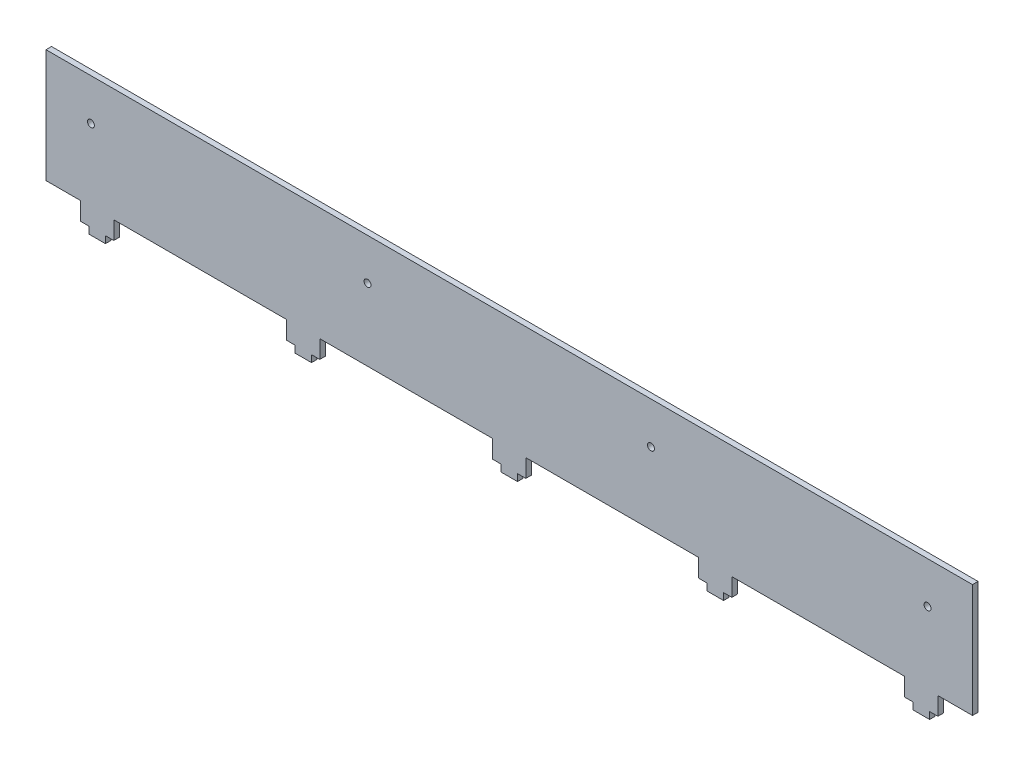
SolidWorks part; units mm, degrees
ref_plane "Спереди" through (0, 0, 0) normal (0, 0, 1) x (1, 0, 0)
ref_plane "Сверху" through (0, 0, 0) normal (0, 1, 0) x (1, 0, 0)
ref_plane "Справа" through (0, 0, 0) normal (1, 0, 0) x (0, 0, -1)
sketch "Эскиз1" plane through (0, 0, 0) normal (0, 0, 1) x (1, 0, 0)
  line L1 (-335, -47.5) -> (335, -47.5)
  line L2 (-335, -47.5) -> (-335, 47.5)
  line L3 (-335, 47.5) -> (335, 47.5)
  line L4 (335, -47.5) -> (335, 47.5)
  line L5 (0, 47.5) -> (0, -47.5) construction
  line L6 (-335, 0) -> (335, 0) construction
  point P0 (0, 0)
  dimension "D1" = 95
  dimension "D2" = 670
extrude "Бобышка-Вытянуть1" add sketch "Эскиз1" along normal mid plane 4
sketch "Эскиз2" plane through (0, 0, 2) normal (0, 0, 1) x (1, 0, 0)
  line L0 (-335, -47.5) -> (335, -47.5) construction
  line L9 (-435, -34.5) -> (-310, -34.5)
  line L10 (-435, -34.5) -> (-435, -47.5)
  line L11 (-435, -47.5) -> (-310, -47.5)
  line L12 (-310, -34.5) -> (-310, -47.5)
  line L13 (335, 47.5) -> (-335, 47.5) construction
  line L14 (-286, -34.5) -> (-161, -34.5)
  line L15 (-286, -34.5) -> (-286, -47.5)
  line L16 (-286, -47.5) -> (-161, -47.5)
  line L17 (-161, -34.5) -> (-161, -47.5)
  line L18 (-137, -34.5) -> (-12, -34.5)
  line L19 (-137, -34.5) -> (-137, -47.5)
  line L20 (-137, -47.5) -> (-12, -47.5)
  line L21 (-12, -34.5) -> (-12, -47.5)
  line L22 (12, -34.5) -> (137, -34.5)
  line L23 (12, -34.5) -> (12, -47.5)
  line L24 (12, -47.5) -> (137, -47.5)
  line L25 (137, -34.5) -> (137, -47.5)
  line L26 (161, -34.5) -> (286, -34.5)
  line L27 (161, -34.5) -> (161, -47.5)
  line L28 (161, -47.5) -> (286, -47.5)
  line L29 (286, -34.5) -> (286, -47.5)
  line L30 (310, -34.5) -> (435, -34.5)
  line L31 (310, -34.5) -> (310, -47.5)
  line L32 (310, -47.5) -> (435, -47.5)
  line L33 (435, -34.5) -> (435, -47.5)
  point P25 (-137, -41)
  point P26 (137, -41)
  dimension "D6" = 125
  dimension "D3" = 125
  dimension "D4" = 125
  dimension "D9" = 125
  dimension "D11" = 125
  dimension "D5" = 24
  dimension "D2" = 24
  dimension "D7" = 24
  dimension "D8" = 24
  dimension "D10" = 24
  dimension "D12" = 125
  dimension "D13" = 12
  dimension "D14" = 82
extrude "Вырез-Вытянуть1" cut sketch "Эскиз2" against normal through all
sketch "Эскиз3" [suppressed] plane through (0, 0, 2) normal (0, 0, 1) x (1, 0, 0)
  line L0 (-328, 5.9544) -> (-328, -6.0456)
  line L1 (-328, -6.0456) -> (-318, -6.0456)
  line L2 (-318, -6.0456) -> (-318, -20.0456)
  line L3 (-318, -20.0456) -> (318, -20.0456)
  line L4 (318, -20.0456) -> (318, -6.0456)
  line L5 (318, -6.0456) -> (328, -6.0456)
  line L6 (328, -6.0456) -> (328, 5.9544)
  line L7 (328, 5.9544) -> (290, 5.9544)
  line L8 (290, 5.9544) -> (280, 35.5)
  line L9 (280, 35.5) -> (240, 35.5)
  line L10 (240, 35.5) -> (230, 5.9544)
  line L11 (230, 5.9544) -> (-230, 5.9544)
  line L12 (-230, 5.9544) -> (-240, 35.5)
  line L13 (-240, 35.5) -> (-280, 35.5)
  line L14 (-280, 35.5) -> (-290, 5.9544)
  line L15 (-290, 5.9544) -> (-328, 5.9544)
  line L16 (0, 0) -> (0, 91.1092) construction
  line L17 (-260, 35.5) -> (-260, 12.7826) construction
  line L18 (260, 35.5) -> (260, 0) construction
  line L19 (-12, -35.0456) -> (-137, -35.0456) construction
  line L20 (-335, 47.5) -> (-335, -35.0456) construction
  line L21 (335, 47.5) -> (-335, 47.5) construction
  dimension "D1" = 15
  dimension "D2" = 14
  dimension "D3" = 12
  dimension "D4" = 60
  dimension "D5" = 38
  dimension "D6" = 7
  dimension "D7" = 17
  dimension "D8" = 12
  dimension "D9" = 40
extrude "Вырез-Вытянуть2" [suppressed] cut sketch "Эскиз3" against normal through all
fillet "Скругление1" [suppressed] radius 10
fillet "Скругление6" [suppressed] radius 2
sketch "Эскиз4" [suppressed] plane through (0, 0, 2) normal (0, 0, 1) x (1, 0, 0)
  circle A1 centre (-302.5, -27.5) radius 2.5
  circle A2 centre (-302.5, -27.5) radius 2.5
  circle A3 centre (0, -27.5) radius 2.5
  circle A4 centre (0, -27.5) radius 2.5
  circle A5 centre (302.5, -27.5) radius 2.5
  circle A6 centre (302.5, -27.5) radius 2.5
  circle A7 centre (-102.5, 17.5) radius 2.5
  circle A8 centre (-102.5, 17.5) radius 2.5
  circle A9 centre (102.5, 17.5) radius 2.5
  circle A10 centre (102.5, 17.5) radius 2.5
  circle A11 centre (-302.5, 17.5) radius 2.5
  circle A12 centre (-302.5, 17.5) radius 2.5
  circle A13 centre (302.5, 17.5) radius 2.5
  circle A14 centre (302.5, 17.5) radius 2.5
  dimension "D1" = 0
  dimension "D2" = 0
  dimension "D3" = 0
  dimension "D4" = 0
  dimension "D5" = 0
  dimension "D6" = 0
  dimension "D7" = 0
extrude "Вырез-Вытянуть3" [suppressed] cut sketch "Эскиз4" against normal through all
sketch "Эскиз5" plane through (0, 0, 2) normal (0, 0, 1) x (1, 0, 0)
  circle A7 centre (-102.5, 17.5) radius 2.5
  circle A8 centre (-102.5, 17.5) radius 2.5
  circle A9 centre (102.5, 17.5) radius 2.5
  circle A10 centre (102.5, 17.5) radius 2.5
  circle A11 centre (-302.5, 17.5) radius 2.5
  circle A12 centre (-302.5, 17.5) radius 2.5
  circle A13 centre (302.5, 17.5) radius 2.5
  circle A14 centre (302.5, 17.5) radius 2.5
  dimension "D4" = 0
  dimension "D5" = 0
  dimension "D6" = 0
  dimension "D7" = 0
extrude "Вырез-Вытянуть4" cut sketch "Эскиз5" against normal through all
sketch "Эскиз6" plane through (0, -47.5, 0) normal (0, -1, 0) x (1, 0, 0)
  line L0 (286, -2) -> (310, -2) construction
  line L2 (310, 2) -> (286, 2) construction
  line L4 (161, 2) -> (137, 2) construction
  line L6 (137, -2) -> (161, -2) construction
  line L8 (-12, -2) -> (12, -2) construction
  line L10 (12, 2) -> (-12, 2) construction
  line L12 (-161, -2) -> (-137, -2) construction
  line L14 (-137, 2) -> (-161, 2) construction
  line L16 (-310, -2) -> (-286, -2) construction
  line L18 (-286, 2) -> (-310, 2) construction
  line L20 (292, -2) -> (304, -2)
  line L21 (304, -2) -> (304, 2)
  line L22 (304, 2) -> (292, 2)
  line L23 (292, 2) -> (292, -2)
  line L24 (155, 2) -> (143, 2)
  line L25 (143, 2) -> (143, -2)
  line L26 (143, -2) -> (155, -2)
  line L27 (155, -2) -> (155, 2)
  line L28 (-6, -2) -> (6, -2)
  line L29 (6, -2) -> (6, 2)
  line L30 (6, 2) -> (-6, 2)
  line L31 (-6, 2) -> (-6, -2)
  line L32 (-155, -2) -> (-143, -2)
  line L33 (-143, -2) -> (-143, 2)
  line L34 (-143, 2) -> (-155, 2)
  line L35 (-155, 2) -> (-155, -2)
  line L36 (-304, -2) -> (-292, -2)
  line L37 (-292, -2) -> (-292, 2)
  line L38 (-292, 2) -> (-304, 2)
  line L39 (-304, 2) -> (-304, -2)
  line L40 (298, 2) -> (298, -2) construction
  line L41 (286, 2) -> (310, 2) construction
  line L42 (149, 2) -> (149, -2) construction
  line L43 (137, 2) -> (161, 2) construction
  line L44 (0, 2) -> (0, -2) construction
  line L45 (-12, 2) -> (12, 2) construction
  line L46 (-149, 2) -> (-149, -2) construction
  line L47 (-161, 2) -> (-137, 2) construction
  line L48 (-298, 2) -> (-298, -2) construction
  line L49 (-310, 2) -> (-286, 2) construction
  point P62 (-292, 0)
  dimension "D1" = 12
  dimension "D2" = 12
  dimension "D3" = 12
  dimension "D4" = 12
  dimension "D5" = 12
extrude "Бобышка-Вытянуть2" add sketch "Эскиз6" along normal blind 5
equation "\"D3@Эскиз2\"=\"D6@Эскиз2\""
equation "\"D4@Эскиз2\"=\"D6@Эскиз2\""
equation "\"D9@Эскиз2\"=\"D6@Эскиз2\""
equation "\"D2@Эскиз2\"=\"D5@Эскиз2\""
equation "\"D7@Эскиз2\"=\"D5@Эскиз2\""
equation "\"D10@Эскиз2\"=\"D5@Эскиз2\""
equation "\"D12@Эскиз2\"=\"D6@Эскиз2\""
equation "\"D13@Эскиз2\"=\"D5@Эскиз2\"/2"
